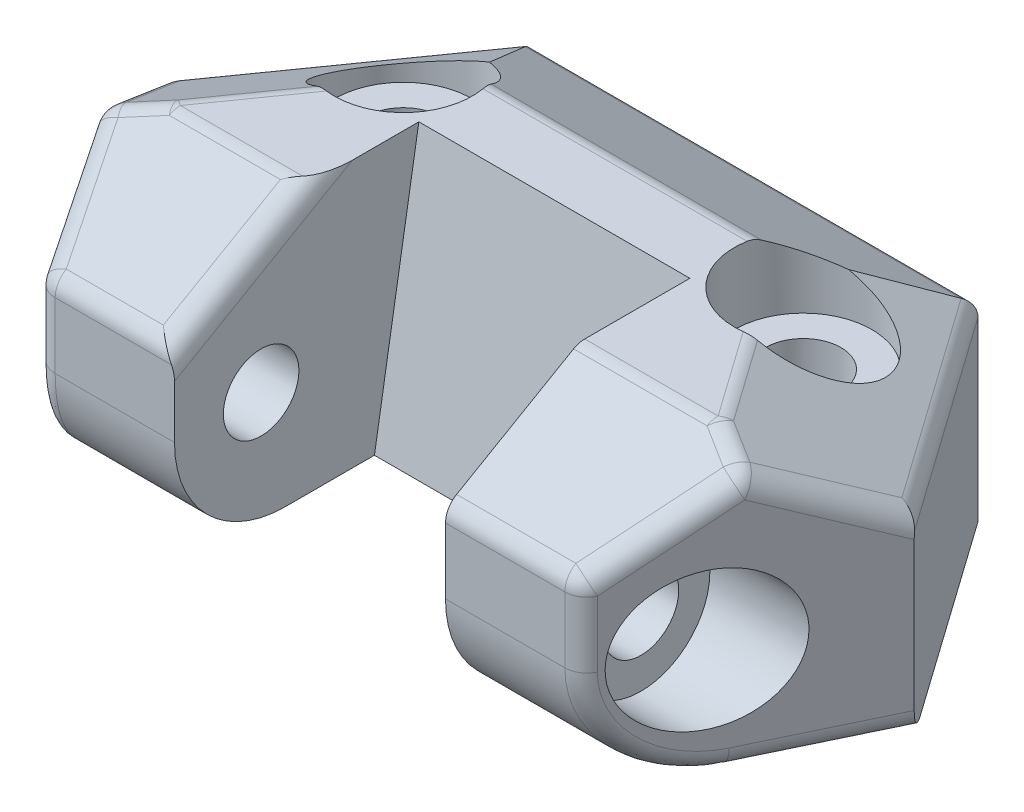
SolidWorks part; units mm, degrees
material "Настроенная пользователем пластмасса"
ref_plane "Front" through (0, 0, 0) normal (0, 0, 1) x (1, 0, 0)
ref_plane "Top" through (0, 0, 0) normal (0, 1, 0) x (1, 0, 0)
ref_plane "Right" through (0, 0, 0) normal (1, 0, 0) x (0, 0, -1)
sketch "Эскиз1" plane through (0, 0, 0) normal (0, 1, 0) x (1, 0, 0)
  line L0 (0, 28.8332) -> (0, -21.8216) construction
  line L1 (-10.0708, 9.5) -> (10.0708, 9.5)
  line L3 (-12.1, -10.5) -> (-6.1, -10.5)
  line L5 (-17, 10) -> (17, -10) construction
  line L6 (-17, -10) -> (17, 10) construction
  line L7 (-6.1, -10.5) -> (-6.1, -1.5)
  line L8 (-6.1, -1.5) -> (6.1, -1.5)
  line L9 (6.1, -10.5) -> (6.1, -1.5)
  line L10 (6.1, -10.5) -> (12.1, -10.5)
  line L11 (-25.1374, 2.7) -> (23.3573, 2.7) construction
  line L12 (-9, 20.117) -> (-9, -17.9041) construction
  line L13 (-35.3276, -0.3) -> (25.3871, -0.3) construction
  line L14 (-12.1, 13.1438) -> (-12.1, -14.0886) construction
  line L15 (-17, -0.3) -> (-10.0708, 9.5)
  line L16 (-17, -0.3) -> (-12.1, -10.5)
  line L17 (17, -0.3) -> (12.1, -10.5)
  line L18 (17, -0.3) -> (10.0708, 9.5)
  circle A0 centre (-9, 2.7) radius 1.7
  circle A1 centre (9, 2.7) radius 1.7
  point P0 (0, 0)
  point P12 (0, -1.5)
  dimension "D7" = 3.4
  dimension "D8" = 9.8
  dimension "D1" = 34
  dimension "D2" = 20
  dimension "D3" = 9
  dimension "D4" = 6.1
  dimension "D5" = 6.8
extrude "Бобышка-Вытянуть1" add sketch "Эскиз1" along normal blind 12
sketch "Эскиз2" plane through (0, 12, 0) normal (0, 1, 0) x (1, 0, 0)
  circle A0 centre (-9, 2.7) radius 3.1
  circle A1 centre (9, 2.7) radius 3.1
  dimension "D1" = 6.2
  dimension "D2" = 6.2
extrude "Вырез-Вытянуть1" cut sketch "Эскиз2" against normal blind 3.2
ref_plane "Плоскость1" through (-17, 0, 0) normal (1, 0, 0) x (0, 0, -1)
sketch "Эскиз3" plane through (-17, 0, 0) normal (1, 0, 0) x (0, 0, -1)
  line L0 (-2, 14.686) -> (-2, -3.2867) construction
  line L1 (-10.5, 12) -> (-10.5, 0) construction
  line L2 (-6.6, 13.2867) -> (-6.6, -3.2867) construction
  line L3 (2.1449, 5.6997) -> (-11.551, 5.6997) construction
  line L4 (-0.3, 0) -> (-10.5, 0) construction
  circle A0 centre (-6.6, 5) radius 1.7
  dimension "D3" = 3.4
  dimension "D4" = 5
  dimension "D1" = 8.5
  dimension "D2" = 4.6
extrude "Вырез-Вытянуть3" cut sketch "Эскиз3" along normal through all
sketch "Эскиз5" plane through (-17, 0, 0) normal (1, 0, 0) x (0, 0, -1)
  circle A0 centre (-6.6, 5) radius 3.1
  dimension "D1" = 6.2
extrude "Вырез-Вытянуть4" cut sketch "Эскиз5" along normal blind 6
ref_plane "Плоскость2" through (0, 0, 0) normal (1, 0, 0) x (0, 0, -1)
mirror "Зеркальное отражение1" about plane through (0, 0, 0) normal (1, 0, 0) of "Вырез-Вытянуть4"
fillet "Скругление1" radius 5 2 edges at (9.1, 0, 10.5) (-9.1, 0, 10.5)
chamfer "Фаска6" distance 6 angle 30 3 edges at (13.5354, 12, -4.6) (0, 12, -9.5) (-13.5354, 12, -4.6) first distance on face at (-9, 12, 0.4)
chamfer "Фаска7" distance 6 angle 30 2 edges at (9.1, 12, 10.5) (-9.1, 12, 10.5) first distance on face at (0, 12, 4.4743)
fillet "Скругление2" radius 1 24 edges at (12.1, 6.7679, 10.5) (15.751, 0, 2.9) (-15.751, 0, 2.9) (-12.1, 6.7679, 10.5) (-13.5667, 11.7174, 4.9894) (-9.3607, 12, 4.5) (-6.1, 10.2679, 7.5) (-9.1, 8.5359, 10.5) (-13.3061, 9.9854, 7.9894) (12.8035, 1.4645, 9.0355) (-12.8035, 1.4645, 9.0355) (9.3607, 12, 4.5) (11.1459, 12, 2.4133) (-11.1459, 12, 2.4133) (0, 12, -3.5) (13.5667, 11.7174, 4.9894) (9.1, 8.5359, 10.5) (13.3061, 9.9854, 7.9894) (15.7561, 9.9854, 2.8894) (13.5354, 8.5359, -4.6) (0, 8.5359, -9.5) (-13.5354, 8.5359, -4.6) (-17, 4.2679, 0.3) (-15.7561, 9.9854, 2.8894)
chamfer "Фаска2" distance 12 distance2 2 1 edges at (0, 12, 1.5) first distance on face at (0, 6, 1.5)
